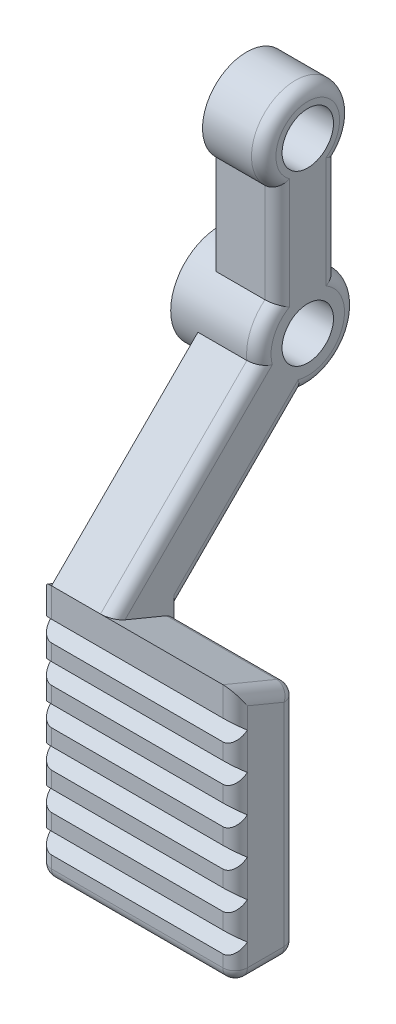
SolidWorks part; units mm, degrees
ref_plane "Front Plane" through (0, 0, 0) normal (1, 0, 0) x (0, 1, 0)
ref_plane "Top Plane" through (0, 0, 0) normal (0, 0, 1) x (0, 1, 0)
ref_plane "Right Plane" through (0, 0, 0) normal (0, 1, 0) x (-1, 0, 0)
sketch "Sketch1" plane through (0, 0, 0) normal (1, 0, 0) x (0, 1, 0)
  line L0 (-1.0607, 4.5962) -> (-12.3995, 15.935)
  line L2 (-33.435, 15.935) -> (-33.435, 10.935)
  line L4 (-12.3995, 15.935) -> (-33.435, 15.935)
  line L5 (4, -2.5) -> (11.2138, -2.5)
  line L6 (-4.5962, 1.0607) -> (-14.4706, 10.935)
  line L7 (-14.4706, 10.935) -> (-33.435, 10.935)
  line L8 (4, 2.5) -> (11.2138, 2.5)
  line L9 (-1.0607, 4.5962) -> (-0.4402, 3.9757)
  line L10 (-4.5962, 1.0607) -> (-3.9757, 0.4402)
  line L11 (3.1225, 2.5) -> (4, 2.5)
  line L12 (3.1225, -2.5) -> (4, -2.5)
  circle A0 centre (0, 0) radius 2.1
  arc A1 (3.1225, 2.5) -> (-0.4402, 3.9757) centre (0, 0) ccw
  circle A2 centre (13.8041, 0) radius 2.1
  arc A3 (-3.9757, 0.4402) -> (3.1225, -2.5) centre (0, 0) ccw
  arc A4 (11.2138, -2.5) -> (11.2138, 2.5) centre (13.8041, 0) ccw
  dimension "D1" = 4.2
  dimension "D2" = 8
  dimension "D3" = 4.2
  dimension "D4" = 7.2
  dimension "D5" = 13.8041
extrude "Boss-Extrude1" add sketch "Sketch1" along normal blind 5
sketch "Sketch2" plane through (0, 0, 0) normal (-1, 0, 0) x (0, -1, 0)
  circle A0 centre (0, 0) radius 4
  circle A1 centre (0, 0) radius 2.1
extrude "Boss-Extrude2" add sketch "Sketch2" along normal blind 2.2
sketch "Sketch3" plane through (0, 0, 0) normal (-1, 0, 0) x (0, 0, 1)
  line L0 (15.935, -12.3995) -> (15.935, -33.435)
  line L1 (15.935, -33.435) -> (10.935, -33.435)
  line L2 (10.935, -33.435) -> (10.935, -14.4706)
  line L3 (15.935, -12.3995) -> (10.935, -14.4706)
extrude "Boss-Extrude3" add sketch "Sketch3" along normal blind 1 and the other way blind 15
fillet "Fillet1" radius 1 11 edges at (-1, -22.9173, 15.935) (-1, -23.9528, 10.935) (-1, -13.435, 13.435) (7, -33.435, 10.935) (-1, -33.435, 13.435) (7, -33.435, 15.935) (15, -23.9528, 10.935) (15, -33.435, 13.435) (15, -22.9173, 15.935) (15, -13.435, 13.435) (10, -14.4706, 10.935)
sketch "Sketch4" plane through (15, 0, 0) normal (1, 0, 0) x (0, 1, 0)
  line L0 (-30.6106, 14.935) -> (-31.4454, 15.935)
  line L1 (-13.8961, 14.935) -> (-32.435, 14.935) construction
  line L2 (-32.435, 15.935) -> (-12.3995, 15.935) construction
  line L3 (-31.4454, 15.935) -> (-29.7672, 15.935)
  line L4 (-29.7672, 15.935) -> (-30.6106, 14.935)
  line L5 (-27.6106, 14.935) -> (-28.4454, 15.935)
  line L6 (-26.7672, 15.935) -> (-27.6106, 14.935)
  line L7 (-24.6106, 14.935) -> (-25.4454, 15.935)
  line L8 (-23.7672, 15.935) -> (-24.6106, 14.935)
  line L9 (-21.6106, 14.935) -> (-22.4454, 15.935)
  line L10 (-20.7672, 15.935) -> (-21.6106, 14.935)
  line L11 (-18.6106, 14.935) -> (-19.4454, 15.935)
  line L12 (-17.7672, 15.935) -> (-18.6106, 14.935)
  line L13 (-15.6106, 14.935) -> (-16.4454, 15.935)
  line L14 (-14.7672, 15.935) -> (-15.6106, 14.935)
  line L15 (-28.4454, 15.935) -> (-26.7672, 15.935)
  line L16 (-25.4454, 15.935) -> (-23.7672, 15.935)
  line L17 (-22.4454, 15.935) -> (-20.7672, 15.935)
  line L18 (-19.4454, 15.935) -> (-17.7672, 15.935)
  line L19 (-16.4454, 15.935) -> (-14.7672, 15.935)
  dimension "D1" = 80
  dimension "D2" = 6
extrude "Cut-Extrude1" cut sketch "Sketch4" against normal through all
fillet "Fillet2" radius 1 7 edges at (5, -9.2231, 5.6876) (5, -6.4198, 9.9554) (5, 1.5307, 3.6955) (5, -1.5307, -3.6955) (5, 7.1681, -2.5) (5, 17.4041, 0) (5, 7.1681, 2.5)
